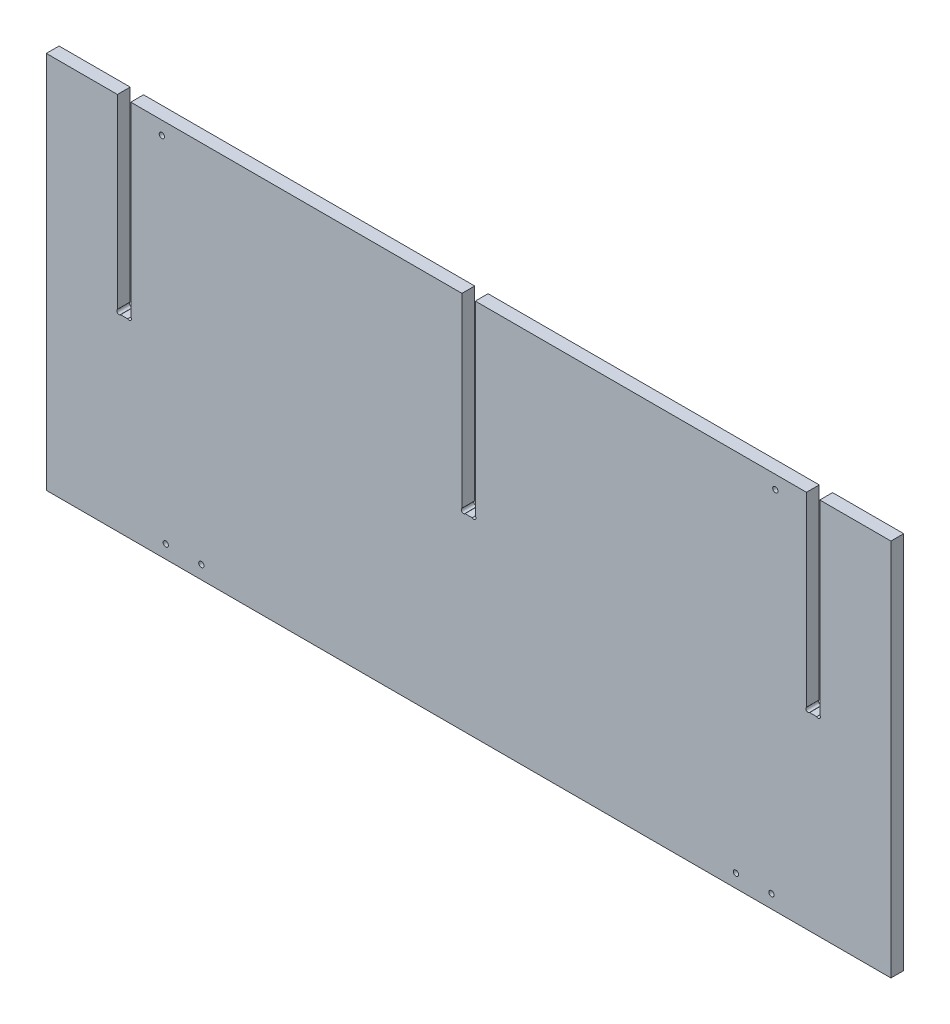
SolidWorks part; units mm, degrees
material "Pine"
ref_plane "Front Plane" through (0, 0, 0) normal (0, 0, 1) x (1, 0, 0)
ref_plane "Top Plane" through (0, 0, 0) normal (0, 1, 0) x (1, 0, 0)
ref_plane "Right Plane" through (0, 0, 0) normal (1, 0, 0) x (0, 0, -1)
sketch "Sketch1" plane through (0, 0, 0) normal (0, 0, 1) x (1, 0, 0)
  line L1 (-684.4008, 298.45) -> (-582.8008, 298.45)
  line L2 (-684.4008, 298.45) -> (-684.4008, -242.0937)
  line L3 (-684.4008, -242.0937) -> (522.0992, -242.0937)
  line L4 (522.0992, 298.45) -> (522.0992, -242.0937)
  line L5 (522.0992, 298.45) -> (420.4992, 298.45) construction
  line L9 (-44.2794, 298.45) -> (401.4492, 298.45)
  line L15 (-684.4008, 298.45) -> (-582.8008, 298.45) construction
  line L17 (420.4992, 298.45) -> (420.4992, 32.6841)
  line L20 (-563.7508, 298.45) -> (-122.4258, 298.45)
  line L22 (-582.8008, 298.45) -> (-582.8008, 32.6841)
  line L25 (420.4992, 298.45) -> (522.0992, 298.45)
  line L26 (-81.1508, -242.0937) -> (-81.1508, 392.0088) construction
  line L27 (-81.1508, -242.0937) -> (-90.6758, -242.0937) construction
  line L28 (-122.4258, 298.45) -> (-90.6758, 298.45)
  line L34 (-90.6758, 298.45) -> (-90.6758, 32.6841)
  line L35 (-86.1857, 28.194) -> (-76.116, 28.194)
  line L36 (-71.6258, 298.45) -> (-71.6258, 32.6841)
  line L37 (-71.6258, 298.45) -> (-44.2794, 298.45)
  line L38 (-81.1508, 28.194) -> (-81.1508, 12.1104) construction
  line L39 (-563.7508, 298.45) -> (-563.7508, 32.684)
  line L41 (401.4492, 298.45) -> (401.4492, 32.5779)
  line L46 (-573.2758, 33.872) -> (-573.2758, 60.4547) construction
  line L47 (-578.3107, 28.194) -> (-570.3254, 28.194) construction
  line L50 (-578.3107, 28.194) -> (-568.241, 28.194)
  line L53 (405.9514, 28.194) -> (416.009, 28.194)
  line L55 (-568.241, 28.194) -> (-568.2408, 28.194)
  arc A21 (-582.8008, 32.6841) -> (-578.3107, 28.194) centre (-580.5558, 30.4391) ccw
  arc A22 (-568.2408, 28.194) -> (-563.7508, 32.684) centre (-566.0142, 30.4573) ccw
  arc A23 (-90.6758, 32.6841) -> (-86.1857, 28.194) centre (-88.4308, 30.4391) ccw
  arc A24 (-76.116, 28.194) -> (-71.6258, 32.6841) centre (-73.8709, 30.4391) ccw
  arc A25 (401.4492, 32.5779) -> (405.9514, 28.194) centre (403.7003, 30.386) ccw
  arc A26 (416.009, 28.194) -> (420.4992, 32.6841) centre (418.2541, 30.4391) ccw
  dimension "D12" = 270.256
  dimension "D13" = 19.05
  dimension "D16" = 19.05
  dimension "D6" = 9.525
  dimension "D8" = 270.256
  dimension "D4" = 270.256
  dimension "D1" = 540.5438
  dimension "D2" = 1206.5
  dimension "D3" = 9.525
  dimension "D5" = 101.6
  dimension "D7" = 101.6
  dimension "D10" = 19.05
extrude "Boss-Extrude1" add sketch "Sketch1" along normal blind 18.2562
hole_wizard "19/64 (0.29688) Diameter Hole1" positions "Sketch2" profile "Sketch3" hole size "19/64" standard "ANSI Inch" end condition through all
sketch "Sketch2" plane through (0, 0, 0) normal (0, 0, -1) x (-1, 0, 0)
  line L1 (684.4008, -242.0937) -> (-522.0992, -242.0937) construction
  line L3 (-401.4492, 298.45) -> (71.6258, 298.45) construction
  line L4 (90.6758, 298.45) -> (563.7508, 298.45) construction
  line L5 (-401.4492, 32.5779) -> (-401.4492, 298.45) construction
  line L6 (563.7508, 298.45) -> (563.7508, 32.684) construction
  point P0 (-351.4429, -223.0437)
  point P4 (-300.6429, -223.0437)
  point P6 (-356.9992, 279.384)
  point P8 (519.3008, 279.4)
  point P10 (513.7446, -223.0437)
  point P12 (462.9446, -223.0437)
  dimension "D2" = 50.8
  dimension "D3" = 19.05
  dimension "D4" = 50.8
  dimension "D5" = 19.05
  dimension "D6" = 50.0062
  dimension "D7" = 44.45
  dimension "D8" = 19.066
  dimension "D9" = 44.45
  dimension "D10" = 19.05
  dimension "D11" = 50.0062
sketch "Sketch3" plane through (351.4429, -223.0437, 0) normal (1, 0, 0) x (0, 1, 0)
  line L0 (0, 0) -> (0, 18.2562)
  line L1 (0, 18.2562) -> (3.7704, 18.2562)
  line L2 (3.7704, 18.2562) -> (3.7704, 0)
  line L5 (3.7704, 0) -> (0, 0)
  line L11 (0, -6.35) -> (0, 107.95) construction
  dimension "Thru Hole Dia." = 7.5408
  dimension "Thru Hole Depth" = 18.2562
